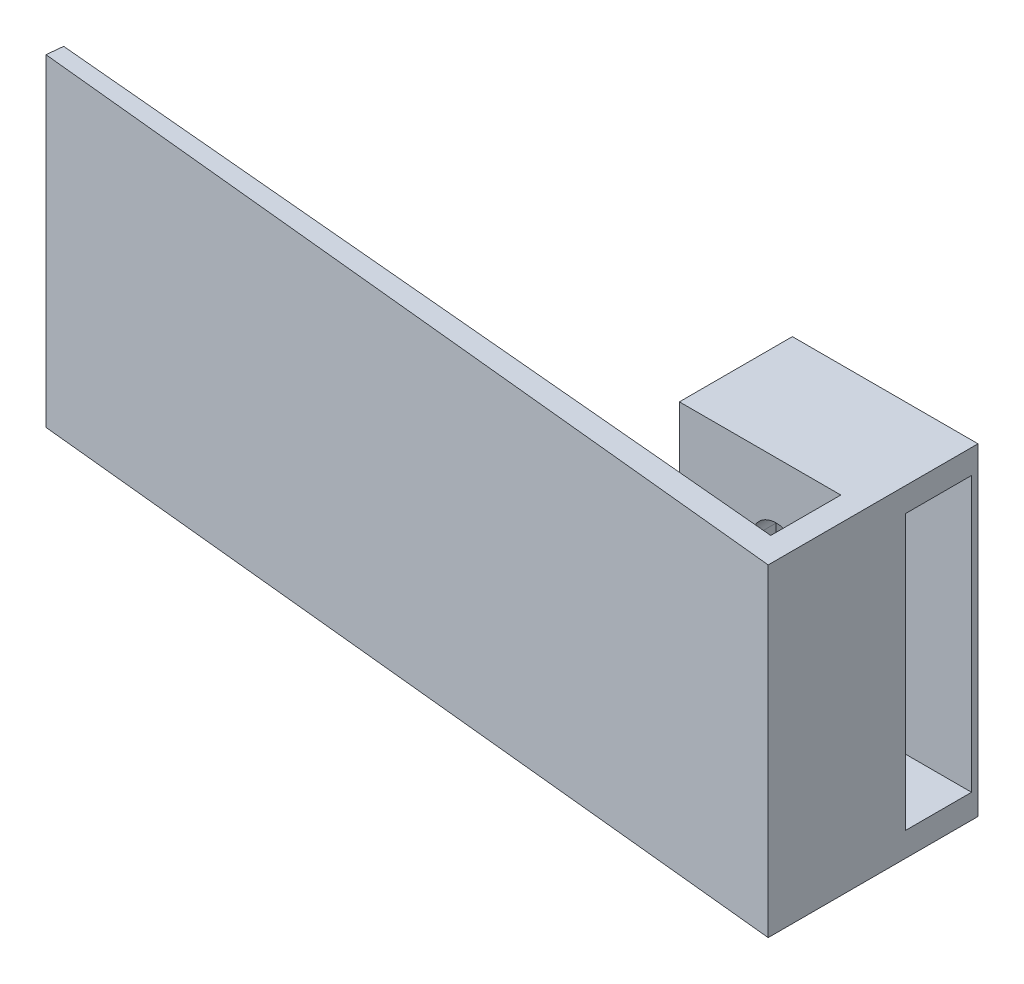
SolidWorks part; units mm, degrees
ref_plane "Alzado" through (0, 0, 0) normal (0, 0, 1) x (1, 0, 0)
ref_plane "Planta" through (0, 0, 0) normal (0, 1, 0) x (1, 0, 0)
ref_plane "Vista lateral" through (0, 0, 0) normal (1, 0, 0) x (0, 0, -1)
sketch "Croquis1" plane through (0, 0, 0) normal (0, 1, 0) x (1, 0, 0)
  line L0 (-11.5, 13) -> (0, 13)
  line L1 (0, 13) -> (0, 0)
  line L2 (0, 0) -> (-49.7489, 5.005)
  line L3 (-49.7489, 5.005) -> (-49.6488, 6)
  line L4 (-49.6488, 6) -> (-1.5, 1.6585)
  line L5 (-1.5, 1.6585) -> (-1.5, 6)
  line L6 (-1.5, 6) -> (-11.5, 6)
  line L7 (-11.5, 6) -> (-11.5, 13)
  line L8 (-111.7842, 6) -> (14.169, 6) construction
  dimension "D1" = 50
  dimension "D2" = 10
  dimension "D3" = 7
  dimension "D4" = 1
  dimension "D5" = 1.5
  dimension "D6" = 13
  dimension "D7" = 1.5
extrude "Saliente-Extruir1" add sketch "Croquis1" along normal blind 20 contours L1 L2 L3 L4 L5 L6 L7 L0
sketch "Croquis4" plane through (0, 0, -13) normal (0, 0, -1) x (-1, 0, 0)
  line L1 (9.5, 1.5) -> (1.5, 1.5)
  line L2 (9.5, 1.5) -> (9.5, 18.5)
  line L3 (9.5, 18.5) -> (1.5, 18.5)
  line L4 (1.5, 1.5) -> (1.5, 18.5)
  line L5 (0, 20) -> (0, 0) construction
  line L6 (1.5, 1.5) -> (0, 1.5)
  line L7 (1.5, 1.5) -> (1.5, 18.5)
  line L8 (1.5, 18.5) -> (0, 18.5)
  line L9 (0, 1.5) -> (0, 18.5)
  line L10 (11.5, 20) -> (11.5, 0) construction
  point P7 (1.5, 10)
  point P9 (11.5, 10)
  point P10 (0, 10)
  line M4 (0, 20) -> (0, 0)
  dimension "D1" = 8
  dimension "D2" = 17
  dimension "D3" = 1.5
extrude "Cortar-Extruir2" cut sketch "Croquis4" against normal blind 5.5 contours L4 L1 L2 L3 region at (-5.5, 10, -13)
extrude "Cortar-Extruir3" cut sketch "Croquis4<4>" against normal blind 4.5 contours L4 L8 L6 M4 region at (-0.75, 10, -13)
sketch "Croquis4<4>" plane through (0, 0, -13) normal (0, 0, -1) x (-1, 0, 0) same geometry as "Croquis4"
sketch "Croquis6" plane through (0, 0, -7.5) normal (0, 0, -1) x (-1, 0, 0)
  line L0 (9.5, 18.5) -> (1.5, 18.5) construction
  line L1 (9.5, 1.5) -> (1.5, 1.5) construction
  line L2 (9.5, 1.5) -> (9.5, 18.5) construction
  line L3 (5.5, 15) -> (5.5, 5) construction
  line L4 (7, 15) -> (7, 5)
  line L5 (4, 15) -> (4, 5)
  arc A0 (7, 15) -> (4, 15) centre (5.5, 15) ccw
  arc A1 (4, 5) -> (7, 5) centre (5.5, 5) ccw
  point P0 (5.5, 18.5)
  point P1 (5.5, 1.5)
  point P4 (9.5, 10)
  point P11 (5.5, 10)
  dimension "D1" = 3
  dimension "D2" = 13
extrude "Cortar-Extruir4" cut sketch "Croquis6" against normal up to next
sketch "Croquis7" plane through (0, 1.5, 0) normal (0, 1, 0) x (1, 0, 0)
  line L0 (0, 8.5) -> (0, 13) construction
  line L1 (-9.5, 13) -> (0, 13)
  line L2 (-9.5, 13) -> (-9.5, 12.6)
  line L3 (-9.5, 12.6) -> (0, 12.6)
  line L4 (0, 13) -> (0, 12.6)
  point P7 (0, 0)
  dimension "D1" = 0.4
extrude "Saliente-Extruir3" add sketch "Croquis7" along normal up to next
